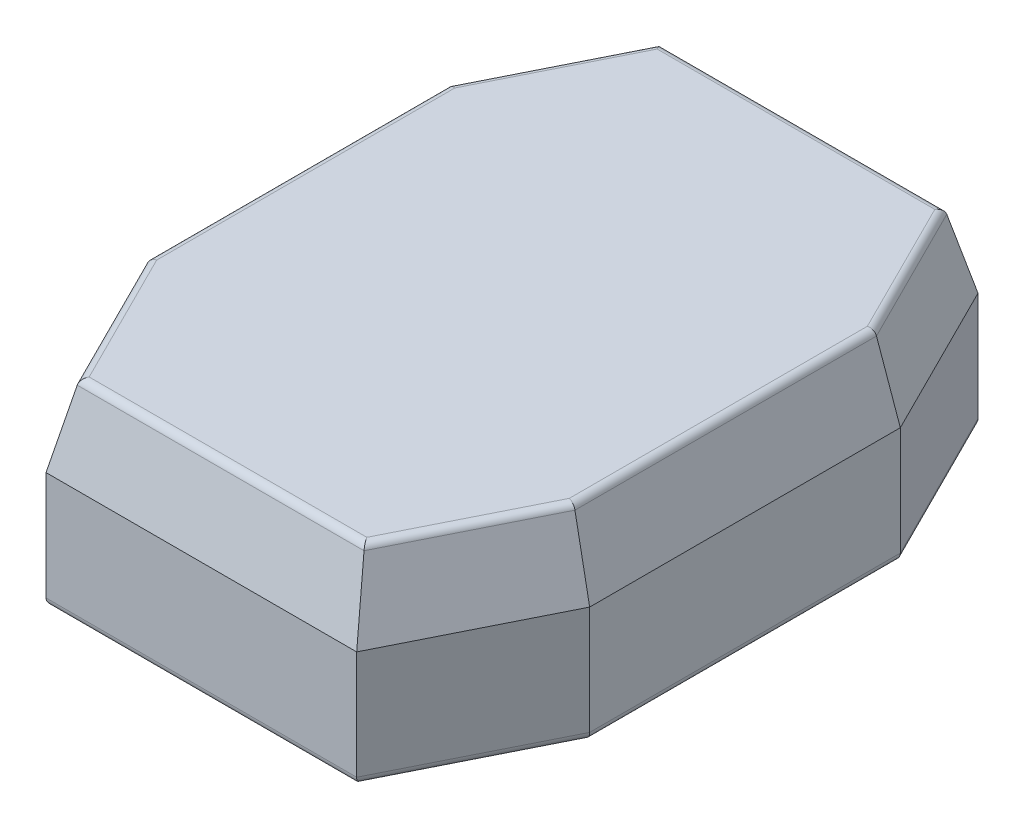
SolidWorks part; units mm, degrees
ref_plane "Front Plane" through (0, 0, 0) normal (0, 0, 1) x (1, 0, 0)
ref_plane "Top Plane" through (0, 0, 0) normal (0, 1, 0) x (1, 0, 0)
ref_plane "Right Plane" through (0, 0, 0) normal (1, 0, 0) x (0, 0, -1)
sketch "Sketch1" plane through (0, 0, 0) normal (0, 1, 0) x (1, 0, 0)
  line L0 (-7.62, 5.08) -> (-5.08, 10.16)
  line L1 (-5.08, 10.16) -> (5.08, 10.16)
  line L2 (-7.62, 5.08) -> (-7.62, -5.08)
  line L3 (-5.08, -10.16) -> (5.08, -10.16)
  line L4 (7.62, 5.08) -> (7.62, -5.08)
  line L5 (-7.62, 10.16) -> (7.62, -10.16) construction
  line L6 (-7.62, -10.16) -> (7.62, 10.16) construction
  line L7 (5.08, 10.16) -> (7.62, 5.08)
  line L8 (5.08, -10.16) -> (7.62, -5.08)
  line L9 (-7.62, -5.08) -> (-5.08, -10.16)
  point P0 (0, 0)
  dimension "D1" = 15.24
  dimension "D2" = 20.32
  dimension "D3" = 2.54
  dimension "D4" = 5.08
  dimension "D5" = 2.54
  dimension "D6" = 5.08
  dimension "D7" = 2.54
  dimension "D8" = 5.08
  dimension "D9" = 5.08
  dimension "D10" = 2.54
extrude "Boss-Extrude1" add sketch "Sketch1" along normal blind 2.54 draft 15
sketch "Stem" plane through (0, 0, 0) normal (0, -1, 0) x (1, 0, 0)
  line L1 (-0.5625, 2.075) -> (0.5625, 2.075)
  line L2 (-0.5625, 2.075) -> (-0.5625, -2.075)
  line L3 (-0.5625, -2.075) -> (0.5625, -2.075)
  line L4 (0.5625, 2.075) -> (0.5625, -2.075)
  line L5 (-0.5625, 2.075) -> (0.5625, -2.075) construction
  line L6 (-0.5625, -2.075) -> (0.5625, 2.075) construction
  line L7 (2.0625, 0.6625) -> (-2.0625, 0.6625)
  line L8 (2.0625, 0.6625) -> (2.0625, -0.6625)
  line L9 (2.0625, -0.6625) -> (-2.0625, -0.6625)
  line L10 (-2.0625, 0.6625) -> (-2.0625, -0.6625)
  line L11 (2.0625, 0.6625) -> (-2.0625, -0.6625) construction
  line L12 (2.0625, -0.6625) -> (-2.0625, 0.6625) construction
  line L13 (-2.5, 2.5) -> (2.5, 2.5)
  line L14 (-3, 2) -> (-3, -2)
  line L15 (-2.5, -2.5) -> (2.5, -2.5)
  line L16 (3, 2) -> (3, -2)
  line L17 (-3, 2.5) -> (3, -2.5) construction
  line L18 (-3, -2.5) -> (3, 2.5) construction
  arc A0 (-3, -2) -> (-2.5, -2.5) centre (-2.5, -2) ccw
  arc A1 (-2.5, 2.5) -> (-3, 2) centre (-2.5, 2) ccw
  arc A2 (2.5, -2.5) -> (3, -2) centre (2.5, -2) ccw
  arc A3 (2.5, 2.5) -> (3, 2) centre (2.5, 2) cw
  point P0 (0, 0)
  point P6 (0, 0)
  point P11 (0, 0)
  dimension "D7" = 0.5
  dimension "D1" = 4.15
  dimension "D2" = 1.125
  dimension "D3" = 1.325
  dimension "D4" = 4.125
  dimension "D5" = 5
  dimension "D6" = 6
extrude "Boss-Extrude2" add sketch "Stem" along normal blind 3.8 contours A3 L13 A1 L14 A0 L15 A2 L16 L10 L7 L2 L1 L4 L8 L9 L3 region at (0, 0, 2.4219)
fillet "Fillet2" radius 0.1 8 edges at (-2.8536, -3.8, -2.3536) (-3, -3.8, 0) (-2.8536, -3.8, 2.3536) (0, -3.8, 2.5) (2.8536, -3.8, 2.3536) (3, -3.8, 0) (2.8536, -3.8, -2.3536) (0, -3.8, -2.5)
chamfer "Chamfer1" distance 0.2 angle 45 11 edges at (-0.5625, -3.8, -1.3688) (-1.3125, -3.8, -0.6625) (-2.0625, -3.8, 0) (0.5625, -3.8, -1.3688) (1.3125, -3.8, -0.6625) (2.0625, -3.8, 0) (1.3125, -3.8, 0.6625) (0.5625, -3.8, 1.3687) (0, -3.8, 2.075) (-0.5625, -3.8, 1.3687) (-1.3125, -3.8, 0.6625)
sketch "Sketch3" plane through (0, 0, 0) normal (0, -1, 0) x (1, 0, 0)
  line L0 (-7.62, 5.08) -> (-7.62, -5.08)
  line L1 (-7.62, -5.08) -> (-5.08, -10.16)
  line L2 (-5.08, -10.16) -> (5.08, -10.16)
  line L3 (5.08, -10.16) -> (7.62, -5.08)
  line L4 (7.62, -5.08) -> (7.62, 5.08)
  line L5 (7.62, 5.08) -> (5.08, 10.16)
  line L6 (5.08, 10.16) -> (-5.08, 10.16)
  line L7 (-5.08, 10.16) -> (-7.62, 5.08)
  line L44 (-6.35, -4.7802) -> (-4.2951, -8.89)
  line L45 (-4.2951, -8.89) -> (4.2951, -8.89)
  line L46 (4.2951, -8.89) -> (6.35, -4.7802)
  line L47 (6.35, -4.7802) -> (6.35, 4.7802)
  line L48 (6.35, 4.7802) -> (4.2951, 8.89)
  line L49 (4.2951, 8.89) -> (-4.2951, 8.89)
  line L50 (-4.2951, 8.89) -> (-6.35, 4.7802)
  line L51 (-6.35, 4.7802) -> (-6.35, -4.7802)
  line L52 (-6.35, -4.7802) -> (-4.2951, -8.89)
  line L53 (-4.2951, -8.89) -> (4.2951, -8.89)
  line L54 (4.2951, -8.89) -> (6.35, -4.7802)
  line L55 (6.35, -4.7802) -> (6.35, 4.7802)
  line L56 (6.35, 4.7802) -> (4.2951, 8.89)
  line L57 (4.2951, 8.89) -> (-4.2951, 8.89)
  line L58 (-4.2951, 8.89) -> (-6.35, 4.7802)
  line L59 (-6.35, 4.7802) -> (-6.35, -4.7802)
  dimension "D1" = 1.27
extrude "Boss-Extrude3" add sketch "Sketch3" along normal blind 3.8
fillet "Fillet3" radius 0.25 16 edges at (0, -3.8, -8.89) (5.3225, -3.8, -6.8351) (6.35, -3.8, 0) (5.3225, -3.8, 6.8351) (0, -3.8, 8.89) (-5.3225, -3.8, 6.8351) (-6.35, -3.8, 0) (-5.3225, -3.8, -6.8351) (0, -3.8, 10.16) (6.35, -3.8, 7.62) (7.62, -3.8, 0) (6.35, -3.8, -7.62) (0, -3.8, -10.16) (-6.35, -3.8, -7.62) (-7.62, -3.8, 0) (-6.35, -3.8, 7.62)
fillet "Fillet5" radius 0.5 16 edges at (0, 0, 2.5) (-2.8536, 0, 2.3536) (-3, 0, 0) (-2.8536, 0, -2.3536) (0, 0, -2.5) (2.8536, 0, -2.3536) (3, 0, 0) (2.8536, 0, 2.3536) (-5.3225, 0, 6.8351) (0, 0, 8.89) (5.3225, 0, 6.8351) (6.35, 0, 0) (5.3225, 0, -6.8351) (0, 0, -8.89) (-5.3225, 0, -6.8351) (-6.35, 0, 0)
fillet "Fillet6" radius 0.1 12 edges at (-1.3125, 0, 0.6625) (-0.5625, 0, 1.3687) (0, 0, 2.075) (0.5625, 0, 1.3687) (1.3125, 0, 0.6625) (2.0625, 0, 0) (1.3125, 0, -0.6625) (0.5625, 0, -1.3688) (0, 0, -2.075) (-0.5625, 0, -1.3688) (-1.3125, 0, -0.6625) (-2.0625, 0, 0)
fillet "Fillet7" radius 0.25 8 edges at (5.7994, 2.54, -7.1994) (6.9394, 2.54, 0) (5.7994, 2.54, 7.1994) (0, 2.54, 9.4794) (-5.7994, 2.54, 7.1994) (-6.9394, 2.54, 0) (-5.7994, 2.54, -7.1994) (0, 2.54, -9.4794)
